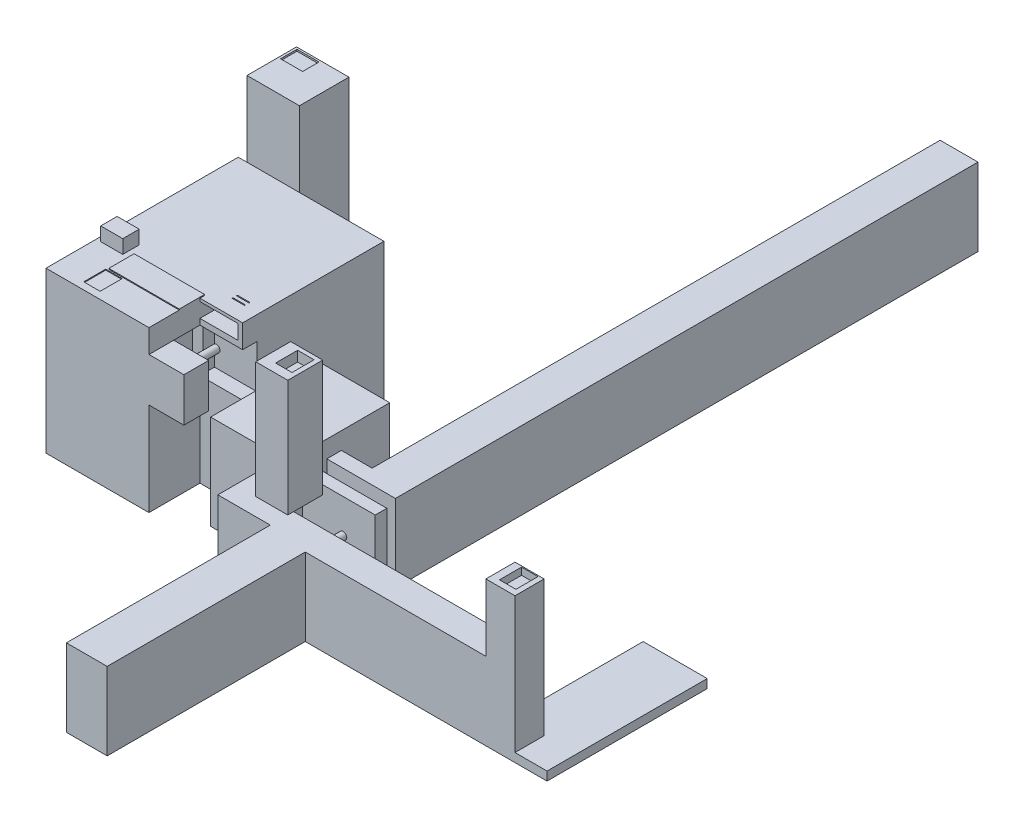
SolidWorks part; units mm, degrees
ref_plane "Front Plane" through (0, 0, 0) normal (0, 0, 1) x (1, 0, 0)
ref_plane "Top Plane" through (0, 0, 0) normal (0, 1, 0) x (1, 0, 0)
ref_plane "Right Plane" through (0, 0, 0) normal (1, 0, 0) x (0, 0, -1)
sketch "Sketch1" plane through (0, 0, 0) normal (0, 1, 0) x (1, 0, 0)
  line L1 (-250, -250) -> (250, -250)
  line L2 (-250, -250) -> (-250, 250)
  line L3 (-250, 250) -> (250, 250)
  line L4 (250, -250) -> (250, 250)
  line L5 (-250, -250) -> (250, 250) construction
  line L6 (-250, 250) -> (250, -250) construction
  point P1 (0, 0)
  dimension "D1" = 500
  dimension "D2" = 500
extrude "Boss-Extrude1" add sketch "Sketch1" along normal blind 550
sketch "Sketch2" plane through (0, 550, 0) normal (0, 1, 0) x (1, 0, 0)
  line L0 (-250, -250) -> (250, -250) construction
  line L1 (-235, -180.8) -> (-159.2, -180.8)
  line L2 (-235, -180.8) -> (-235, -237.2)
  line L3 (-235, -237.2) -> (-159.2, -237.2)
  line L4 (-159.2, -180.8) -> (-159.2, -237.2)
  line L5 (-235, -180.8) -> (-159.2, -237.2) construction
  line L6 (-235, -237.2) -> (-159.2, -180.8) construction
  line L7 (-250, 250) -> (-250, -250) construction
  point P0 (-197.1, -209)
  dimension "D1" = 12.8
  dimension "D2" = 56.4
  dimension "D3" = 15
  dimension "D4" = 75.8
extrude "Boss-Extrude2" add sketch "Sketch2" along normal blind 46.8
ref_plane "Plane1" through (0, 0, 211.7) normal (0, 0, 1) x (1, 0, 0)
ref_plane "Plane2" through (-138.6, 0, 0) normal (1, 0, 0) x (0, 0, -1)
sketch "Sketch5" plane through (-138.6, 0, 0) normal (1, 0, 0) x (0, 0, -1)
  line L5 (-250, 550) -> (-219, 550)
  line L6 (-250, 550) -> (-250, 553.15)
  line L7 (-250, 553.15) -> (-219, 553.15)
  line L8 (-219, 550) -> (-219, 553.15)
  dimension "D1" = 3.15
  dimension "D2" = 31
extrude "Boss-Extrude4" add sketch "Sketch5" along normal blind 242
sketch "Sketch6" plane through (0, 550, 0) normal (0, 1, 0) x (1, 0, 0)
  line L0 (250, -250) -> (250, 250) construction
  line L1 (103.4, -250) -> (250, -250)
  line L2 (103.4, -250) -> (103.4, -235)
  line L3 (103.4, -235) -> (250, -235)
  line L4 (250, -250) -> (250, -235)
  dimension "D1" = 15
extrude "Cut-Extrude2" cut sketch "Sketch6" against normal through all
sketch "Sketch7" plane through (0, 0, 250) normal (0, 0, 1) x (1, 0, 0)
  line L1 (-250, 550) -> (103.4, 550)
  line L2 (-250, 550) -> (-250, 0)
  line L3 (-250, 0) -> (103.4, 0)
  line L4 (103.4, 550) -> (103.4, 0)
extrude "Boss-Extrude5" add sketch "Sketch7" along normal blind 160
sketch "Sketch8" plane through (0, 0, 250) normal (0, 0, 1) x (1, 0, 0)
  line L0 (-138.6, -25.74) -> (-138.6, 25.74) construction
  line L1 (103.4, 553.15) -> (-138.6, 553.15)
  line L2 (103.4, 553.15) -> (103.4, 550)
  line L3 (103.4, 550) -> (-138.6, 550)
  line L4 (-138.6, 553.15) -> (-138.6, 550)
  line L5 (103.4, 550) -> (-138.6, 550) construction
extrude "Boss-Extrude6" add sketch "Sketch8" along normal blind 55.8
sketch "Sketch9" plane through (0, 550, 0) normal (0, 1, 0) x (1, 0, 0)
  line L0 (103.4, -410) -> (-250, -410) construction
  line L1 (-144.8, -385.8) -> (-88.4, -385.8)
  line L2 (-144.8, -385.8) -> (-144.8, -310)
  line L3 (-144.8, -310) -> (-88.4, -310)
  line L4 (-88.4, -385.8) -> (-88.4, -310)
  line L5 (-250, 250) -> (-250, -410) construction
  dimension "D1" = 24.2
  dimension "D2" = 56.4
  dimension "D3" = 75.8
  dimension "D4" = 105.2
extrude "Cut-Extrude3" cut sketch "Sketch9" against normal blind 3.25
sketch "Sketch12" plane through (0, 550, 0) normal (0, 1, 0) x (1, 0, 0)
  line L0 (250, -235) -> (250, 250) construction
  line L1 (200, -176.7) -> (160, -176.7)
  line L3 (200, -180.1) -> (160, -180.1)
  line L5 (250, -235) -> (103.4, -235) construction
  arc A0 (200, -180.1) -> (200, -176.7) centre (200, -178.4) ccw
  arc A1 (160, -176.7) -> (160, -180.1) centre (160, -178.4) ccw
  dimension "D1" = 3.4
  dimension "D3" = 40
  dimension "D4" = 50
  dimension "D5" = 56.6
extrude "Cut-Extrude6" cut sketch "Sketch12" against normal blind 10
sketch "Sketch13" plane through (0, 0, 235) normal (0, 0, 1) x (1, 0, 0)
  line L0 (103.4, 0) -> (103.4, 550) construction
  line L1 (103.4, 540) -> (233.4, 540)
  line L2 (103.4, 540) -> (103.4, 490)
  line L3 (103.4, 490) -> (233.4, 490)
  line L4 (233.4, 540) -> (233.4, 490)
  line L5 (250, 550) -> (103.4, 550) construction
  dimension "D1" = 10
  dimension "D2" = 50
  dimension "D3" = 130
extrude "Cut-Extrude7" cut sketch "Sketch13" against normal blind 130
pattern_linear "LPattern1" count 2 spacing 15 along (0, 0, -1) of "Cut-Extrude6"
sketch "Sketch14" plane through (0, 0, 235) normal (0, 0, 1) x (1, 0, 0)
  line L0 (103.4, 0) -> (103.4, 490) construction
  line L1 (103.4, 320) -> (250, 320)
  line L2 (103.4, 320) -> (103.4, 470)
  line L3 (103.4, 470) -> (250, 470)
  line L4 (250, 320) -> (250, 470)
  line L5 (250, 550) -> (103.4, 550) construction
  line L6 (250, 0) -> (250, 550) construction
  dimension "D1" = 80
  dimension "D2" = 0
  dimension "D3" = 150
extrude "Cut-Extrude8" cut sketch "Sketch14" against normal blind 50
sketch "Sketch15" plane through (250, 0, 0) normal (1, 0, 0) x (0, 0, -1)
  line L0 (-235, 0) -> (-410, 0) construction
  line L5 (-345, 0) -> (5, 0)
  line L6 (-345, 0) -> (-345, 325)
  line L7 (-345, 325) -> (5, 325)
  line L8 (5, 0) -> (5, 325)
  line L9 (-235, 0) -> (-235, 320) construction
  dimension "D1" = 325
  dimension "D2" = 110
  dimension "D3" = 350
extrude "Boss-Extrude7" add sketch "Sketch15" along normal blind 265
sketch "Sketch16" plane through (515, 0, 0) normal (1, 0, 0) x (0, 0, -1)
  line L0 (-345, 0) -> (5, 0) construction
  line L1 (-211, 0) -> (-161, 0)
  line L2 (-211, 0) -> (-211, 266.2)
  line L3 (-211, 266.2) -> (-161, 266.2)
  line L4 (-161, 0) -> (-161, 266.2)
  line L5 (5, 0) -> (5, 325) construction
  dimension "D1" = 50
  dimension "D2" = 266.2
  dimension "D3" = 216
extrude "Boss-Extrude8" add sketch "Sketch16" along normal blind 235.5
sketch "Sketch17" plane through (0, 0, 161) normal (0, 0, -1) x (-1, 0, 0)
  line L12 (-750.5, 266.2) -> (-515, 266.2) construction
  line L13 (-620.5, 266.2) -> (-750.5, 266.2)
  line L14 (-620.5, 266.2) -> (-620.5, 0)
  line L15 (-620.5, 0) -> (-750.5, 0)
  line L16 (-750.5, 266.2) -> (-750.5, 0)
  line L17 (-750.5, 0) -> (-750.5, 266.2) construction
  dimension "D1" = 130
  dimension "D2" = 0
extrude "Boss-Extrude9" add sketch "Sketch17" along normal blind 1950
sketch "Sketch18" plane through (0, 0, 345) normal (0, 0, 1) x (1, 0, 0)
  line L7 (515, 0) -> (435, 0)
  line L8 (515, 0) -> (515, 266.2)
  line L9 (515, 266.2) -> (435, 266.2)
  line L10 (435, 0) -> (435, 266.2)
  dimension "D1" = 80
extrude "Boss-Extrude10" add sketch "Sketch18" along normal blind 160
sketch "Sketch19" plane through (515, 0, 0) normal (1, 0, 0) x (0, 0, -1)
  line L0 (-505, 266.2) -> (-345, 266.2) construction
  line L1 (-425, 266.2) -> (-1205, 266.2)
  line L2 (-425, 266.2) -> (-425, 0)
  line L3 (-425, 0) -> (-1205, 0)
  line L4 (-1205, 266.2) -> (-1205, 0)
  line L5 (-505, 0) -> (-505, 266.2) construction
  dimension "D1" = 700
  dimension "D2" = 80
extrude "Boss-Extrude11" add sketch "Sketch19" along normal blind 240
sketch "Sketch20" plane through (515, 0, 0) normal (-1, 0, 0) x (0, 0, 1)
  line L0 (1205, 0) -> (505, 0) construction
  line L1 (505, 266.2) -> (1205, 266.2)
  line L2 (505, 266.2) -> (505, 0)
  line L3 (505, 0) -> (1205, 0)
  line L4 (1205, 266.2) -> (1205, 0)
extrude "Cut-Extrude9" cut sketch "Sketch20" against normal blind 100
sketch "Sketch21" plane through (755, 0, 0) normal (1, 0, 0) x (0, 0, -1)
  line L0 (-1205, 0) -> (-425, 0) construction
  line L1 (-425, 266.2) -> (-525, 266.2)
  line L2 (-425, 266.2) -> (-425, 0)
  line L3 (-425, 0) -> (-525, 0)
  line L4 (-525, 266.2) -> (-525, 0)
  dimension "D1" = 100
extrude "Boss-Extrude12" add sketch "Sketch21" along normal blind 720
sketch "Sketch22" plane through (0, 266.2, 0) normal (0, 1, 0) x (1, 0, 0)
  line L0 (1475, -525) -> (755, -525) construction
  line L1 (1475, -425) -> (1375, -425)
  line L2 (1475, -425) -> (1475, -525)
  line L3 (1475, -525) -> (1375, -525)
  line L4 (1375, -425) -> (1375, -525)
  dimension "D1" = 100
extrude "Boss-Extrude14" add sketch "Sketch22" along normal blind 230
sketch "Sketch23" plane through (0, 496.2, 0) normal (0, 1, 0) x (1, 0, 0)
  line L0 (1475, -525) -> (1475, -425) construction
  line L1 (1401.1, -428.55) -> (1457.5, -428.55)
  line L2 (1401.1, -428.55) -> (1401.1, -504.35)
  line L3 (1401.1, -504.35) -> (1457.5, -504.35)
  line L4 (1457.5, -428.55) -> (1457.5, -504.35)
  line L5 (1475, -425) -> (1375, -425) construction
  dimension "D1" = 75.8
  dimension "D2" = 56.4
  dimension "D3" = 17.5
  dimension "D4" = 3.55
extrude "Cut-Extrude10" cut sketch "Sketch23" against normal blind 24.4
sketch "Sketch24" plane through (515, 0, 0) normal (1, 0, 0) x (0, 0, -1)
  line L0 (-425, 0) -> (-211, 0) construction
  line L1 (-295, 0) -> (-255, 0)
  line L2 (-295, 0) -> (-295, 266.2)
  line L3 (-295, 266.2) -> (-255, 266.2)
  line L4 (-255, 0) -> (-255, 266.2)
  line L5 (-425, 0) -> (-425, 266.2) construction
  dimension "D1" = 130
  dimension "D2" = 40
extrude "Boss-Extrude15" add sketch "Sketch24" along normal blind 250
sketch "Sketch25" plane through (0, 0, 295) normal (0, 0, 1) x (1, 0, 0)
  line L0 (435, 0) -> (615, 0) construction
  line L1 (515, 325) -> (515, 266.2) construction
  circle A0 centre (655, 150) radius 12.5
  dimension "D1" = 25
  dimension "D2" = 150
  dimension "D3" = 140
extrude "Boss-Extrude16" add sketch "Sketch25" along normal up to next
sketch "Sketch26" plane through (0, 266.2, 0) normal (0, 1, 0) x (1, 0, 0)
  line L0 (615, -505) -> (435, -505) construction
  line L1 (505, -445) -> (615, -445)
  line L2 (505, -445) -> (505, -325)
  line L3 (505, -325) -> (615, -325)
  line L4 (615, -445) -> (615, -325)
  line L5 (435, -505) -> (435, -345) construction
  dimension "D1" = 120
  dimension "D2" = 110
  dimension "D3" = 60
  dimension "D4" = 70
extrude "Boss-Extrude22" add sketch "Sketch26" along normal blind 365.6
sketch "Sketch28" plane through (0, 631.8, 0) normal (0, 1, 0) x (1, 0, 0)
  line L0 (615, -445) -> (615, -325) construction
  line L1 (542.78, -338.9) -> (599.18, -338.9)
  line L2 (542.78, -338.9) -> (542.78, -414.7)
  line L3 (542.78, -414.7) -> (599.18, -414.7)
  line L4 (599.18, -338.9) -> (599.18, -414.7)
  line L5 (505, -445) -> (615, -445) construction
  line L7 (505, -325) -> (615, -325)
  line L8 (505, -325) -> (505, -445)
  line L9 (505, -445) -> (615, -445)
  line L10 (615, -325) -> (615, -445)
  dimension "D1" = 15.82
  dimension "D2" = 30.3
  dimension "D3" = 75.8
  dimension "D4" = 56.4
extrude "Boss-Extrude23" add sketch "Sketch28" along normal blind 35
sketch "Sketch29" plane through (103.4, 0, 0) normal (1, 0, 0) x (0, 0, -1)
  line L0 (-185, 470) -> (-185, 320) construction
  line L1 (-325, 470) -> (-225, 470)
  line L2 (-325, 470) -> (-325, 320)
  line L3 (-325, 320) -> (-225, 320)
  line L4 (-225, 470) -> (-225, 320)
  line L5 (-410, 550) -> (-305.8, 550) construction
  dimension "D1" = 40
  dimension "D2" = 100
  dimension "D3" = 150
  dimension "D4" = 80
extrude "Cut-Extrude11" cut sketch "Sketch29" against normal blind 35
sketch "Sketch30" plane through (103.4, 0, 0) normal (1, 0, 0) x (0, 0, -1)
  line L0 (-410, 0) -> (-410, 550) construction
  line L1 (-325, 470) -> (-410, 470)
  line L2 (-325, 470) -> (-325, 320)
  line L3 (-325, 320) -> (-410, 320)
  line L4 (-410, 470) -> (-410, 320)
extrude "Boss-Extrude24" add sketch "Sketch30" along normal blind 120
sketch "Sketch31" plane through (0, 0, 325) normal (0, 0, -1) x (-1, 0, 0)
  line L0 (-68.4, 320) -> (-103.4, 320) construction
  line L1 (-68.4, 470) -> (-68.4, 320) construction
  circle A0 centre (-109.9, 378.75) radius 12.5
  dimension "D3" = 25
  dimension "D1" = 58.75
  dimension "D2" = 41.5
extrude "Boss-Extrude25" add sketch "Sketch31" along normal up to next
sketch "Sketch32" plane through (0, 0, 0) normal (0, -1, 0) x (1, 0, 0)
  line L5 (1475, 525) -> (755, 525) construction
  line L6 (1365, 525) -> (1585, 525)
  line L7 (1365, 525) -> (1365, -25)
  line L8 (1365, -25) -> (1585, -25)
  line L9 (1585, 525) -> (1585, -25)
  line L10 (1475, 525) -> (1475, 425) construction
  dimension "D1" = 110
  dimension "D2" = 220
  dimension "D3" = 550
extrude "Boss-Extrude26" add sketch "Sketch32" against normal blind 30
sketch "Sketch34" plane through (0, 0, -250) normal (0, 0, -1) x (-1, 0, 0)
  line L0 (-250, 0) -> (250, 0) construction
  line L1 (40, 0) -> (220, 0)
  line L2 (40, 0) -> (40, 808)
  line L3 (40, 808) -> (220, 808)
  line L4 (220, 0) -> (220, 808)
  line L5 (250, 550) -> (250, 0) construction
  dimension "D1" = 808
  dimension "D2" = 180
  dimension "D3" = 30
extrude "Boss-Extrude28" add sketch "Sketch34" along normal blind 170
sketch "Sketch35" plane through (0, 808, 0) normal (0, 1, 0) x (1, 0, 0)
  line L0 (-220, 420) -> (-40, 420) construction
  line L1 (-136.3, 413.6) -> (-212.1, 413.6)
  line L2 (-136.3, 413.6) -> (-136.3, 357.2)
  line L3 (-136.3, 357.2) -> (-212.1, 357.2)
  line L4 (-212.1, 413.6) -> (-212.1, 357.2)
  line L5 (-220, 420) -> (-220, 250) construction
  dimension "D1" = 75.8
  dimension "D2" = 56.4
  dimension "D3" = 6.4
  dimension "D4" = 7.9
extrude "Cut-Extrude12" cut sketch "Sketch35" against normal blind 5.8
